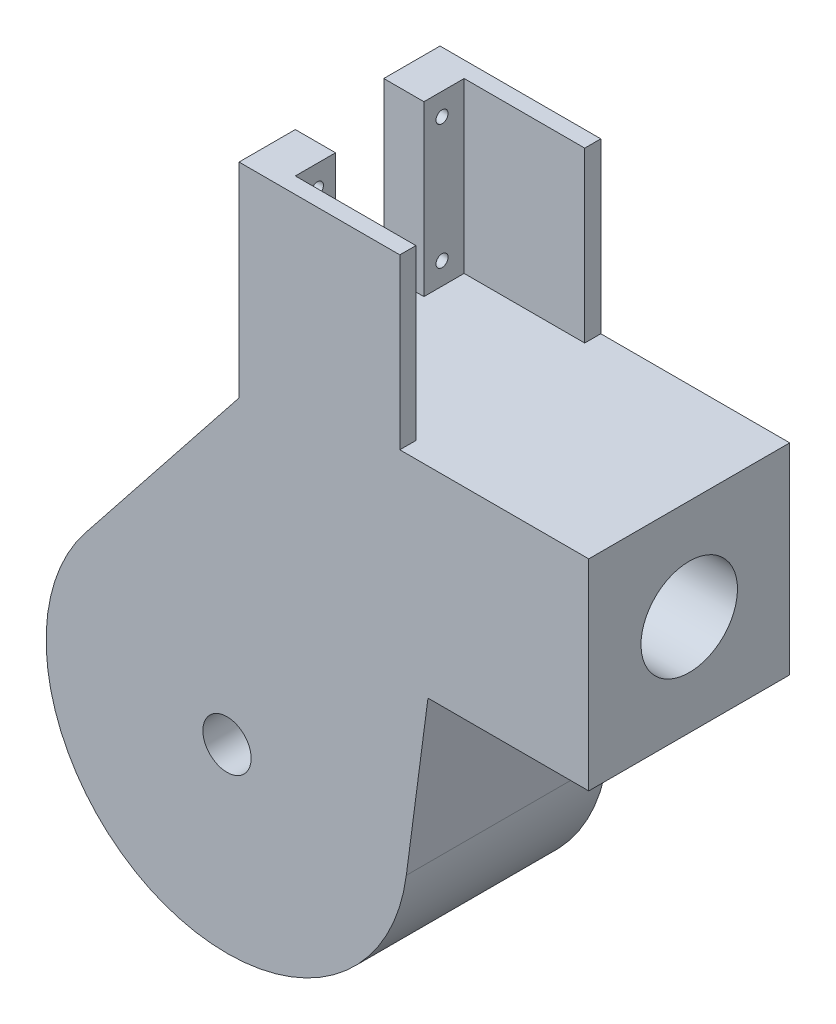
SolidWorks part; units mm, degrees
ref_plane "Front Plane" through (0, 0, 0) normal (0, 0, 1) x (1, 0, 0)
ref_plane "Top Plane" through (0, 0, 0) normal (0, 1, 0) x (1, 0, 0)
ref_plane "Right Plane" through (0, 0, 0) normal (1, 0, 0) x (0, 0, -1)
sketch "Sketch1" plane through (0, 0, 0) normal (0, 0, 1) x (1, 0, 0)
  line L0 (50, 35) -> (44.6145, -5.8778)
  line L1 (90, 85) -> (50, 85)
  line L2 (90, 85) -> (90, 35)
  line L3 (90, 35) -> (50, 35)
  line L4 (50, 85) -> (50, 35)
  line L5 (90, 85) -> (50, 35) construction
  line L6 (90, 35) -> (50, 85) construction
  line L7 (50, 85) -> (10, 85)
  line L8 (10, 85) -> (-35.2511, 27.9707)
  circle A0 centre (0, 0) radius 45
  point P3 (70, 60)
  dimension "D1" = 90
  dimension "D2" = 70
  dimension "D3" = 40
  dimension "D4" = 50
  dimension "D5" = 60
  dimension "D6" = 40
extrude "Boss-Extrude1" add sketch "Sketch1" along normal blind 50 contours L1 L4 L3 L2 | A0 L0 L4 L7 L8 | A0 region at (70, 60, 0) region at (23.7004, 56.6095, 0) region at (0, 0, 0)
sketch "Sketch3" plane through (90, 0, 0) normal (1, 0, 0) x (0, 0, -1)
  line L0 (-50, 85) -> (0, 35) construction
  line L1 (0, 35) -> (0, 85) construction
  line L2 (0, 85) -> (-50, 35) construction
  line L3 (-50, 85) -> (-50, 35) construction
  line L4 (-50, 35) -> (0, 35) construction
  circle A0 centre (-25, 60) radius 12
  dimension "D1" = 24
extrude "Cut-Extrude1" cut sketch "Sketch3" against normal blind 130
ref_plane "Plane1" through (-40, 0, 0) normal (-1, 0, 0) x (0, 0, 1)
sketch "Sketch6" plane through (0, 85, 0) normal (0, 1, 0) x (1, 0, 0)
  line L0 (90, 0) -> (10, 0) construction
  line L18 (43, 0) -> (3, 0)
  line L19 (43, 0) -> (43, -4)
  line L20 (43, -4) -> (3, -4)
  line L21 (3, 0) -> (3, -4)
  line L22 (90, -50) -> (10, -50) construction
  line L23 (43, -50) -> (3, -50)
  line L24 (43, -50) -> (43, -46)
  line L25 (43, -46) -> (3, -46)
  line L26 (3, -50) -> (3, -46)
  line L27 (13, -14) -> (13, -36) construction
  line L28 (3, -46) -> (13, -46)
  line L29 (3, -46) -> (3, -36)
  line L30 (3, -36) -> (13, -36)
  line L31 (13, -46) -> (13, -36)
  line L32 (3, -4) -> (13, -4)
  line L33 (3, -4) -> (3, -14)
  line L34 (3, -14) -> (13, -14)
  line L35 (13, -4) -> (13, -14)
  line L36 (13, -25) -> (-8, -25) construction
  line M15 (90, 0) -> (10, 0)
  line M16 (10, 0) -> (10, -50)
  line M17 (10, -50) -> (90, -50)
  dimension "D1" = 42
  dimension "D2" = 4
  dimension "D3" = 22
  dimension "D4" = 10
  dimension "D5" = 3
  dimension "D6" = 10
  dimension "D7" = 30
extrude "Boss-Extrude3" add sketch "Sketch6" along normal blind 42 and the other way blind 10 contours L20 L19 M15 M16 | L18 L21 L20 M16 | L33 L34 L20 M16 | L35 L20 L34 M16 | L25 L31 L30 M16 | L30 L29 L25 M16 | L26 L23 L25 M16 | L24 L25 M16 M17 region at (26.5, 85, 2) region at (11.5, 85, 41) region at (6.5, 85, 41) region at (6.5, 85, 2) region at (6.5, 85, 9) region at (11.5, 85, 9) region at (6.5, 85, 48) region at (26.5, 85, 48)
sketch "Sketch5" plane through (-40, 0, 0) normal (-1, 0, 0) x (0, 0, 1)
  line L1 (46, 40) -> (4, 40)
  line L2 (46, 40) -> (46, 80)
  line L3 (46, 80) -> (4, 80)
  line L4 (4, 40) -> (4, 80)
  line L5 (46, 40) -> (4, 80) construction
  line L6 (46, 80) -> (4, 40) construction
  point P0 (25, 60)
  dimension "D1" = 42
  dimension "D2" = 40
extrude "Cut-Extrude2" cut sketch "Sketch5" against normal up to surface (43 mm away) and the other way blind 11 up to face at (3, 101.589, 7)
sketch "Sketch9" plane through (13, 0, 0) normal (1, 0, 0) x (0, 0, -1)
  line L0 (-46, 127) -> (-4, 85) construction
  line L2 (-4, 127) -> (-46, 85) construction
  arc A0 (-39.4035, 122.5235) -> (-41.5235, 120.4035) centre (-25, 106) ccw
  circle A1 centre (-9.5002, 121.4998) radius 1.5
  circle A2 centre (-9.5002, 90.5002) radius 1.5
  circle A3 centre (-40.4998, 90.5002) radius 1.5
  circle A4 centre (-40.4998, 121.4998) radius 1.5
  arc A5 (-41.5235, 91.5965) -> (-39.4035, 89.4765) centre (-25, 106) ccw
  arc A6 (-10.5965, 89.4765) -> (-8.4765, 91.5965) centre (-25, 106) ccw
  arc A8 (-8.4765, 120.4035) -> (-10.5965, 122.5235) centre (-25, 106) ccw
  point P20 (-25, 106)
  dimension "D1" = 4
extrude "Cut-Extrude4" cut sketch "Sketch9" against normal blind 10 contours A0 A4 | A0 A4 | A0 A1 | A0 A1 | A0 A2 | A0 A2 | A0 A3 | A0 A3 region at (13, 121.0431, 40.0431) region at (13, 121.9433, 40.9433) region at (13, 121.9433, 9.0567) region at (13, 121.0431, 9.9569) region at (13, 90.0567, 9.0567) region at (13, 90.9569, 9.9569) region at (13, 90.9569, 40.0431) region at (13, 90.0567, 40.9433)
sketch "Skizze1" plane through (0, 0, 0) normal (0, 0, -1) x (-1, 0, 0)
  circle A0 centre (0, 0) radius 6
  dimension "D1" = 12
extrude "Schnitt-Linear austragen1" cut sketch "Skizze1" against normal up to surface (50 mm away) up to face at (34.3469, 59.9769, 50)
sketch "Skizze2" plane through (0, 0, 0) normal (0, 0, -1) x (-1, 0, 0)
  circle A0 centre (0, 0) radius 6
  circle A1 centre (0, 0) radius 17.5
  circle A2 centre (0, 0) radius 6 construction
  dimension "D1" = 35
extrude "Aufsatz-Linear austragen1" add sketch "Skizze2" along normal blind 36
sketch "Skizze3" plane through (0, 0, 0) normal (0, 0, -1) x (-1, 0, 0)
  circle A0 centre (0, 0) radius 17.5
  circle A1 centre (0, 0) radius 21.5
  circle A2 centre (0, 0) radius 17.5 construction
  dimension "D1" = 43
extrude "Aufsatz-Linear austragen2" add sketch "Skizze3" along normal blind 1
sketch "Skizze4" plane through (0, 0, -36) normal (0, 0, -1) x (-1, 0, 0)
  line L0 (-6, 0) -> (-17.5, 0) construction
  circle A0 centre (0, 0) radius 6 construction
  circle A1 centre (0, 0) radius 17.5 construction
  circle A2 centre (-11.75, 0) radius 1.65
  circle A3 centre (-5.875, 10.1758) radius 1.65
  circle A4 centre (5.875, 10.1758) radius 1.65
  circle A5 centre (11.75, 0) radius 1.65
  circle A6 centre (5.875, -10.1758) radius 1.65
  circle A7 centre (-5.875, -10.1758) radius 1.65
  point P21 (0, 0)
  dimension "D1" = 6
extrude "Schnitt-Linear austragen2" cut sketch "Skizze4" against normal blind 15
